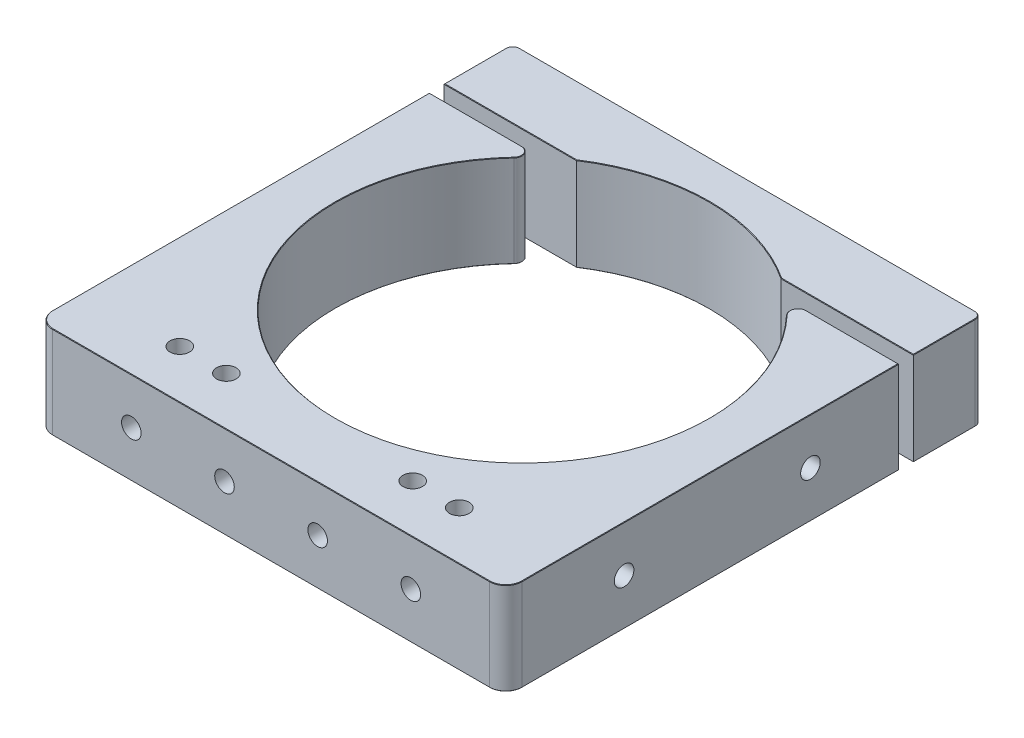
SolidWorks part; units mm, degrees
material "6061-T6 (SS)"
ref_plane "Front Plane" through (0, 0, 0) normal (0, 0, 1) x (1, 0, 0)
ref_plane "Top Plane" through (0, 0, 0) normal (0, 1, 0) x (1, 0, 0)
ref_plane "Right Plane" through (0, 0, 0) normal (1, 0, 0) x (0, 0, -1)
sketch "Sketch1" plane through (0, 0, 0) normal (0, 1, 0) x (1, 0, 0)
  line L0 (0, 0) -> (0, -53.925) construction
  line L1 (-50.375, -53.925) -> (50.375, -53.925)
  line L2 (-50.375, -53.925) -> (-50.375, 30.425)
  line L3 (-50.375, 30.425) -> (-26.1598, 30.425)
  line L4 (50.375, 30.425) -> (26.1598, 30.425)
  line L5 (50.375, -53.925) -> (50.375, 30.425)
  line L6 (-50.375, 33.575) -> (-50.375, 48.325)
  line L7 (-50.375, 33.575) -> (-21.9712, 33.575)
  line L8 (-50.375, 48.325) -> (50.375, 48.325)
  line L9 (50.375, 33.575) -> (50.375, 48.325)
  line L10 (-50.375, 33.575) -> (50.375, 48.325) construction
  line L11 (-50.375, 48.325) -> (50.375, 33.575) construction
  line L12 (21.9712, 33.575) -> (50.375, 33.575)
  arc A0 (21.9712, 33.575) -> (-21.9712, 33.575) centre (0, 0) ccw
  arc A1 (-26.1598, 30.425) -> (26.1598, 30.425) centre (0, 0) ccw
  point P3 (0, -40.125)
  point P7 (0, -53.925)
  point P13 (0, 40.95)
  point P15 (0, 40.125)
  dimension "D1" = 80.25
  dimension "D2" = 100.75
  dimension "D3" = 13.8
  dimension "D4" = 84.35
  dimension "D5" = 14.75
  dimension "D6" = 8.2
extrude "Boss-Extrude1" add sketch "Sketch1" along normal mid plane 19.8 contours A1 L3 L2 L1 L5 L4 region at (-49.061, 0, 11.75)
extrude "Boss-Extrude2" add sketch "Sketch1<3>" along normal mid plane 20 separate body contours A0 L12 L9 L8 L6 L7 region at (0, 0, -41.6663)
sketch "Sketch1<3>" plane through (0, 0, 0) normal (0, 1, 0) x (1, 0, 0) same geometry as "Sketch1"
fillet "Fillet1" radius 3.5 2 edges at (-50.375, 0, 53.925) (50.375, 0, 53.925)
fillet "Fillet2" radius 1.75 2 edges at (26.1598, 0, -30.425) (-26.1598, 0, -30.425)
sketch "Sketch2" plane through (0, 0, 53.925) normal (0, 0, 1) x (1, 0, 0)
  line L0 (-50.375, 0) -> (50.375, 0) construction
  line L1 (-50.375, -9.9) -> (-50.375, 9.9) construction
  line L2 (0, 0) -> (0, 10) construction
  line L3 (21.9712, 10) -> (-21.9712, 10) construction
  point P4 (0, 0)
  point P11 (10, 0)
  point P12 (-10, 0)
  point P13 (30, 0)
  point P14 (-30, 0)
  dimension "D1" = 20
  dimension "D2" = 20
  dimension "D3" = 20
hole_wizard "M5x0.8 Tapped Hole1" positions "Sketch3" profile "Sketch4" tap size "M5x0.8" standard "ANSI Metric"
sketch "Sketch3" plane through (0, 0, 53.925) normal (0, 0, 1) x (1, 0, 0)
  point P0 (-30, 0)
  point P3 (-10, 0)
  point P6 (10, 0)
  point P9 (30, 0)
sketch "Sketch4" plane through (-30, 0, 53.925) normal (1, 0, 0) x (0, -1, 0)
  line L0 (0, 0) -> (0, 11.6618)
  line L1 (0, 11.6618) -> (2.1, 10.4)
  line L2 (2.1, 10.4) -> (2.1, 0)
  line L5 (2.1, 0) -> (0, 0)
  line L10 (0, 11.6618) -> (-2.1, 10.4) construction
  line L11 (0, -6.35) -> (0, 107.95) construction
  dimension "Tap Drill Dia." = 4.2
  dimension "Tap Drill Depth" = 10.4
  dimension "Drill Angle" = 118
cosmetic thread "Hole Thread1" parameters "D1"=8, "D2"=5
cosmetic thread "Hole Thread2" parameters "D1"=8, "D2"=5
cosmetic thread "Hole Thread3" parameters "D1"=8, "D2"=5
cosmetic thread "Hole Thread4" parameters "D1"=8, "D2"=5
sketch "Sketch5" plane through (50.375, 0, 0) normal (1, 0, 0) x (0, 0, -1)
  line L0 (-53.925, 0) -> (30.425, 0) construction
  line L1 (-53.925, -9.9) -> (-53.925, 9.9) construction
  line L2 (30.425, 9.9) -> (30.425, -9.9) construction
  point P6 (-28.525, 0)
  point P7 (11.475, 0)
  dimension "D1" = 25.4
  dimension "D2" = 40
hole_wizard "M5x0.8 Tapped Hole2" positions "Sketch6" profile "Sketch7" tap size "M5x0.8" standard "ANSI Metric"
sketch "Sketch6" plane through (50.375, 0, 0) normal (1, 0, 0) x (0, 0, -1)
  point P0 (-28.525, 0)
  point P3 (11.475, 0)
sketch "Sketch7" plane through (50.375, 0, 28.525) normal (0, 1, 0) x (0, 0, -1)
  line L0 (0, 0) -> (0, 11.6618)
  line L1 (0, 11.6618) -> (2.1, 10.4)
  line L2 (2.1, 10.4) -> (2.1, 0)
  line L5 (2.1, 0) -> (0, 0)
  line L10 (0, 11.6618) -> (-2.1, 10.4) construction
  line L11 (0, -6.35) -> (0, 107.95) construction
  dimension "Tap Drill Dia." = 4.2
  dimension "Tap Drill Depth" = 10.4
  dimension "Drill Angle" = 118
cosmetic thread "Hole Thread5" parameters "D1"=8, "D2"=5
cosmetic thread "Hole Thread6" parameters "D1"=8, "D2"=5
mirror "Mirror1" about plane through (0, 0, 0) normal (1, 0, 0) of "M5x0.8 Tapped Hole2"
sketch "Sketch8" plane through (0, 0, -48.325) normal (0, 0, -1) x (-1, 0, 0)
  line L1 (-25, -6.5) -> (25, -6.5)
  line L2 (-27.5, -4) -> (-27.5, 4)
  line L3 (-25, 6.5) -> (25, 6.5)
  line L4 (27.5, -4) -> (27.5, 4)
  line L5 (0, 6.5) -> (0, -6.5) construction
  line L6 (-27.5, 0) -> (27.5, 0) construction
  arc A0 (25, -6.5) -> (27.5, -4) centre (25, -4) ccw
  arc A1 (25, 6.5) -> (27.5, 4) centre (25, 4) cw
  arc A2 (-25, -6.5) -> (-27.5, -4) centre (-25, -4) cw
  arc A3 (-27.5, 4) -> (-25, 6.5) centre (-25, 4) cw
  point P0 (0, 0)
  point P11 (27.5, 6.5)
  point P16 (-27.5, 6.5)
  dimension "D3" = 2.5
  dimension "D1" = 55
  dimension "D2" = 13
extrude "Cut-Extrude1" cut sketch "Sketch8" against normal blind 1
sketch "Sketch9" plane through (0, 0, -48.325) normal (0, 0, -1) x (-1, 0, 0)
  line L0 (0, -10) -> (0, 10) construction
  line L1 (50.375, -10) -> (-50.375, -10) construction
  line L2 (50.375, 10) -> (-50.375, 10) construction
  line L3 (-41.6, 0) -> (41.6, 0) construction
  circle A0 centre (-41.6, 0) radius 3.05
  circle A1 centre (41.6, 0) radius 3.05
  point P10 (0, 0)
  dimension "D2" = 6.1
  dimension "D1" = 83.2
extrude "Cut-Extrude2" cut sketch "Sketch9" against normal up to next (14.75 mm away)
hole_wizard "M5x0.8 Tapped Hole3" positions "Sketch12" profile "Sketch13" tap size "M5x0.8" standard "ANSI Metric"
sketch "Sketch12" plane through (0, 0, -30.425) normal (0, 0, -1) x (-1, 0, 0)
  point P0 (-41.6, 0)
  point P3 (41.6, 0)
sketch "Sketch13" plane through (41.6, 0, -30.425) normal (1, 0, 0) x (0, 1, 0)
  line L0 (0, 0) -> (0, 22.6618)
  line L1 (0, 22.6618) -> (2.1, 21.4)
  line L2 (2.1, 21.4) -> (2.1, 0)
  line L5 (2.1, 0) -> (0, 0)
  line L10 (0, 22.6618) -> (-2.1, 21.4) construction
  line L11 (0, -6.35) -> (0, 107.95) construction
  dimension "Tap Drill Dia." = 4.2
  dimension "Tap Drill Depth" = 21.4
  dimension "Drill Angle" = 118
cosmetic thread "Hole Thread7" parameters "D1"=19, "D2"=5
cosmetic thread "Hole Thread8" parameters "D1"=19, "D2"=5
sketch "Sketch20" plane through (0, 0, -48.325) normal (0, 0, -1) x (-1, 0, 0)
  circle A0 centre (-41.6, 0) radius 5.09
  circle A1 centre (41.6, 0) radius 5.09
  dimension "D1" = 10.18
extrude "Cut-Extrude4" cut sketch "Sketch20" against normal blind 1.5
chamfer "Chamfer1" distance 0.1 angle 45 22 edges at (-28.9104, -9.9, -29.3698) (-40.4458, -9.9, -30.425) (-50.375, -9.9, 10) (-49.3499, -9.9, 52.8999) (0, -9.9, 53.925) (49.3499, -9.9, 52.8999) (50.375, -9.9, 10) (0, -9.9, 40.125) (28.9104, -9.9, -29.3698) (40.4458, -9.9, -30.425) (50.375, 9.9, 10) (49.3499, 9.9, 52.8999) (0, 9.9, 53.925) (-49.3499, 9.9, 52.8999) (-50.375, 9.9, 10) (50.375, 0, -30.425) (40.4458, 9.9, -30.425) (28.9104, 9.9, -29.3698) (0, 9.9, 40.125) (-28.9104, 9.9, -29.3698) (-40.4458, 9.9, -30.425) (-50.375, 0, -30.425)
fillet "Fillet3" radius 1.5 2 edges at (50.375, 0, -48.325) (-50.375, 0, -48.325)
chamfer "Chamfer2" distance 0.1 angle 45 16 edges at (-49.9357, -10, -47.8857) (-50.375, -10, -40.2) (-36.1731, -10, -33.575) (0, -10, -40.125) (36.1731, -10, -33.575) (50.375, -10, -40.2) (49.9357, -10, -47.8857) (0, -10, -48.325) (36.1731, 10, -33.575) (0, 10, -40.125) (-36.1731, 10, -33.575) (-50.375, 10, -40.2) (-49.9357, 10, -47.8857) (0, 10, -48.325) (49.9357, 10, -47.8857) (50.375, 10, -40.2)
sketch "Sketch14" plane through (0, 9.9, 0) normal (0, 1, 0) x (1, 0, 0)
  line L0 (0, 0) -> (0, -53.925) construction
  line L1 (-46.875, -53.925) -> (46.875, -53.925) construction
  point P5 (20, -43.525)
  point P6 (30, -43.525)
  point P9 (-20, -43.525)
  point P10 (-30, -43.525)
  dimension "D1" = 10.4
  dimension "D2" = 30
  dimension "D3" = 10
hole_wizard "M5x0.8 Tapped Hole4" positions "Sketch15" profile "Sketch16" tap size "M5x0.8" standard "ANSI Metric" end condition through all
sketch "Sketch15" plane through (0, 9.9, 0) normal (0, 1, 0) x (1, 0, 0)
  point P0 (-30, -43.525)
  point P3 (-20, -43.525)
  point P6 (20, -43.525)
  point P9 (30, -43.525)
sketch "Sketch16" plane through (-30, 9.9, 43.525) normal (1, 0, 0) x (0, 0, 1)
  line L0 (0, 0) -> (0, 19.9)
  line L1 (0, 19.9) -> (2.1, 19.9)
  line L2 (2.1, 19.9) -> (2.1, 0)
  line L5 (2.1, 0) -> (0, 0)
  line L11 (0, -6.35) -> (0, 107.95) construction
  dimension "Thru Tap Drill Dia." = 4.2
  dimension "Thru Tap Drill Depth" = 19.9
cosmetic thread "Hole Thread9" parameters "D2"=5
cosmetic thread "Hole Thread10" parameters "D2"=5
cosmetic thread "Hole Thread11" parameters "D2"=5
cosmetic thread "Hole Thread12" parameters "D2"=5
sketch "Sketch17" plane through (0, 0, -47.325) normal (0, 0, -1) x (-1, 0, 0)
  line L0 (-25.4642, -4) -> (25.4642, -4) construction
  line L2 (-25, -6.5) -> (25, -6.5) construction
  text T0 "Ø 80mm" font "Century Gothic" height 8
  point P2 (0, -4)
  dimension "D1" = 2.5
extrude "Cut-Extrude3" cut sketch "Sketch17" against normal blind 0.001
